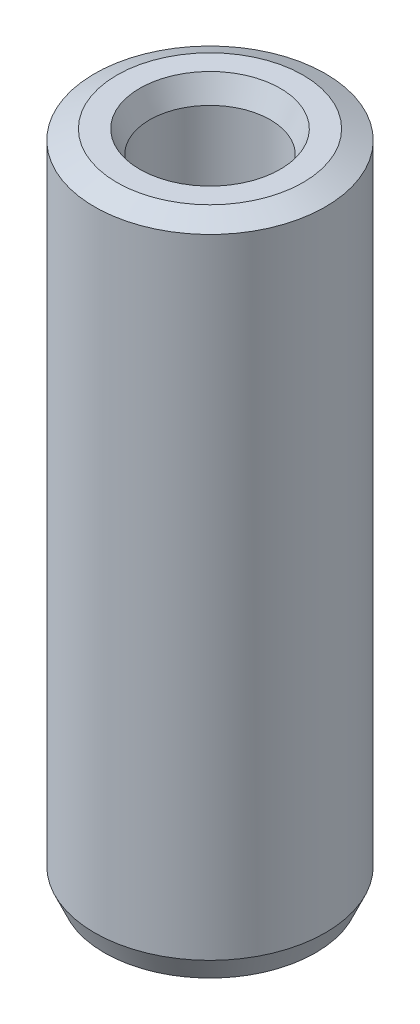
SolidWorks part; units mm, degrees
ref_plane "Front Plane" through (0, 0, 0) normal (0, 0, 1) x (1, 0, 0)
ref_plane "Top Plane" through (0, 0, 0) normal (0, 1, 0) x (1, 0, 0)
ref_plane "Right Plane" through (0, 0, 0) normal (1, 0, 0) x (0, 0, -1)
sketch "Sketch1" plane through (0, 0, 0) normal (0, 1, 0) x (1, 0, 0)
  circle A0 centre (0, 0) radius 7.5
  dimension "SLEEVE_OD" = 15
extrude "Boss-Extrude1" add sketch "Sketch1" along normal blind 42.9436
sketch "Sketch2" plane through (0, 0, 0) normal (0, 1, 0) x (1, 0, 0)
  circle A0 centre (0, 0) radius 3.9206
  dimension "BORE_D" = 7.8412
extrude "Cut-Extrude1" cut sketch "Sketch2" along normal through all
chamfer "Chamfer1" distance 0.6438 angle 66.092 4 edges at (0, 42.9436, 3.9206) (0, 0, 3.9206) (0, 0, 7.5) (0, 42.9436, 7.5) first distance on face at (0, 42.9436, 3.9206) first distance on face at (0, 0, 3.9206) first distance on face at (0, 42.9436, 7.5)
